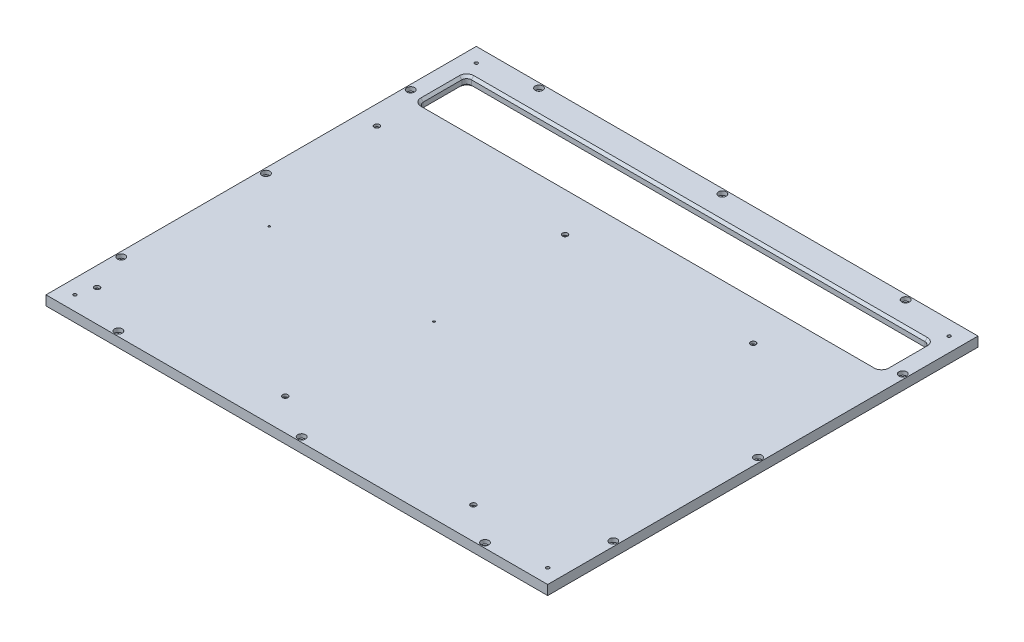
SolidWorks part; units mm, degrees
material "Bakelite Black"
ref_plane "Front" through (0, 0, 0) normal (0, 0, 1) x (1, 0, 0)
ref_plane "Top" through (0, 0, 0) normal (0, 1, 0) x (1, 0, 0)
ref_plane "Right" through (0, 0, 0) normal (1, 0, 0) x (0, 0, -1)
sketch "Sketch1" plane through (0, 0, 0) normal (0, 1, 0) x (1, 0, 0)
  line L1 (0, 0) -> (520, 0)
  line L2 (0, 0) -> (0, 446)
  line L3 (0, 446) -> (520, 446)
  line L4 (520, 0) -> (520, 446)
  dimension "D1" = 520
  dimension "D2" = 446
extrude "Boss-Extrude1" add sketch "Sketch1" along normal blind 10
sketch "Sketch4" plane through (0, 10, 0) normal (0, 1, 0) x (1, 0, 0)
  line L0 (520, 446) -> (0, 446) construction
  line L1 (500, 366) -> (20, 366)
  line L2 (500, 366) -> (500, 416)
  line L3 (500, 416) -> (20, 416)
  line L4 (20, 366) -> (20, 416)
  line L6 (260, 416) -> (260, 0) construction
  line L7 (20, 391) -> (500, 391) construction
  line L8 (0, 0) -> (520, 0) construction
  dimension "D1" = 240
  dimension "D2" = 30
  dimension "D3" = 50
extrude "Cut-Extrude1" cut sketch "Sketch4" against normal blind 10
fillet "Fillet1" radius 5 4 edges at (500, 5, -366) (20, 5, -416) (500, 5, -416) (20, 5, -366)
chamfer "Chamfer1" distance 2.5 angle 45 16 edges at (21.4645, 10, -367.4645) (260, 10, -366) (498.5355, 10, -367.4645) (500, 10, -391) (498.5355, 10, -414.5355) (260, 10, -416) (21.4645, 10, -414.5355) (20, 10, -391) (21.4645, 0, -367.4645) (20, 0, -391) (21.4645, 0, -414.5355) (260, 0, -416) (498.5355, 0, -414.5355) (500, 0, -391) (498.5355, 0, -367.4645) (260, 0, -366)
ref_plane "Plane1" through (260, 0, 0) normal (-1, 0, 0) x (0, 0, 1)
ref_plane "Plane2" through (0, 0, -223) normal (0, 0, 1) x (1, 0, 0)
hole_wizard "CBORE for M4 SHCS1" positions "Sketch5" profile "Sketch6" counterbore size "M4" standard "ANSI Metric"
sketch "Sketch5" plane through (0, 10, 0) normal (0, 1, 0) x (1, 0, 0)
  line L0 (260, 5.5) -> (260, -5.5) construction
  line L1 (-5.5, 223) -> (5.5, 223) construction
  line L3 (0, 0) -> (520, 0) construction
  line L4 (520, 446) -> (0, 446) construction
  line L5 (0, 446) -> (0, 0) construction
  line L6 (520, 0) -> (520, 446) construction
  point P0 (5, 373)
  point P2 (5, 223)
  point P4 (5, 73)
  point P6 (70, 5)
  point P8 (260, 5)
  point P10 (450, 5)
  point P12 (515, 73)
  point P14 (515, 223)
  point P16 (515, 373)
  point P18 (450, 441)
  point P20 (260, 441)
  point P22 (70, 441)
  dimension "D1" = 150
  dimension "D2" = 150
  dimension "D3" = 190
  dimension "D4" = 190
  dimension "D5" = 5
  dimension "D6" = 5
  dimension "D7" = 5
  dimension "D8" = 5
sketch "Sketch6" plane through (5, 10, -373) normal (1, 0, 0) x (0, 0, 1)
  line L0 (0, 0) -> (0, 13.3519)
  line L1 (0, 13.3519) -> (2.25, 12)
  line L2 (2.25, 12) -> (2.25, 4)
  line L3 (2.25, 4) -> (4, 4)
  line L4 (4, 4) -> (4, 0)
  line L5 (4, 0) -> (0, 0)
  line L10 (0, 13.3519) -> (-2.25, 12) construction
  line L11 (0, -6.35) -> (0, 107.95) construction
  dimension "Hole Dia." = 4.5
  dimension "Hole Depth" = 12
  dimension "C'Bore Dia." = 8
  dimension "C'Bore Depth" = 4
  dimension "Drill Angle" = 118
hole_wizard "M4x0.7 Tapped Hole1" positions "Sketch7" profile "Sketch8" tap size "M4x0.7" standard "ANSI Metric" end condition through all
sketch "Sketch7" plane through (0, 10, 0) normal (0, 1, 0) x (1, 0, 0)
  line L0 (520, 446) -> (0, 446) construction
  line L1 (0, 446) -> (0, 0) construction
  line L2 (520, 0) -> (520, 446) construction
  line L3 (0, 0) -> (520, 0) construction
  point P0 (15, 431)
  point P2 (505, 431)
  point P4 (15, 15)
  point P6 (505, 15)
  dimension "D1" = 15
  dimension "D2" = 15
  dimension "D3" = 15
  dimension "D4" = 15
sketch "Sketch8" plane through (15, 10, -431) normal (1, 0, 0) x (0, 0, 1)
  line L0 (0, 0) -> (0, 10)
  line L1 (0, 10) -> (1.65, 10)
  line L2 (1.65, 10) -> (1.65, 0)
  line L5 (1.65, 0) -> (0, 0)
  line L11 (0, -6.35) -> (0, 107.95) construction
  dimension "Thru Tap Drill Dia." = 3.3
  dimension "Thru Tap Drill Depth" = 10
cosmetic thread "Hole Thread1" parameters "D2"=4
cosmetic thread "Hole Thread2" parameters "D2"=4
cosmetic thread "Hole Thread3" parameters "D2"=4
cosmetic thread "Hole Thread4" parameters "D2"=4
hole_wizard "CBORE for M2.5 SHCS1" positions "Sketch9" profile "Sketch10" counterbore size "M2.5" standard "ANSI Metric" end condition through all
sketch "Sketch9" plane through (0, 10, 0) normal (0, 1, 0) x (1, 0, 0)
  line L0 (-5.5, 223) -> (5.5, 223) construction
  line L1 (260, 5.5) -> (260, -5.5) construction
  point P0 (20, 33)
  point P7 (215, 33)
  point P9 (410, 33)
  point P11 (410, 323)
  point P13 (215, 323)
  point P15 (20, 323)
  dimension "D1" = 190
  dimension "D2" = 240
  dimension "D3" = 290
  dimension "D4" = 195
  dimension "D5" = 195
sketch "Sketch10" plane through (20, 10, -33) normal (1, 0, 0) x (0, 0, 1)
  line L0 (0, 0) -> (0, 10)
  line L1 (0, 10) -> (1.45, 10)
  line L3 (1.45, 10) -> (1.45, 2.5)
  line L4 (1.45, 2.5) -> (2.75, 2.5)
  line L5 (2.75, 2.5) -> (2.75, 0)
  line L7 (2.75, 0) -> (0, 0)
  line L11 (0, -6.35) -> (0, 107.95) construction
  dimension "Thru Hole Dia." = 2.9
  dimension "Thru Hole Depth" = 10
  dimension "C'Bore Dia." = 5.5
  dimension "C'Bore Depth" = 2.5
hole_wizard "M2.5x0.45 Tapped Hole1" positions "Sketch11" profile "Sketch12" tap size "M2.5x0.45" standard "ANSI Metric" end condition through all
sketch "Sketch11" plane through (0, 10, 0) normal (0, 1, 0) x (1, 0, 0)
  line L0 (-5.5, 223) -> (5.5, 223) construction
  line L1 (260, 5.5) -> (260, -5.5) construction
  point P0 (54.288, 177.0876)
  point P2 (225.088, 177.0876)
  dimension "D1" = 170.8
  dimension "D2" = 45.9124
  dimension "D3" = 205.712
sketch "Sketch12" plane through (54.288, 10, -177.0876) normal (1, 0, 0) x (0, 0, 1)
  line L0 (0, 0) -> (0, 10)
  line L1 (0, 10) -> (1.025, 10)
  line L2 (1.025, 10) -> (1.025, 0)
  line L5 (1.025, 0) -> (0, 0)
  line L11 (0, -6.35) -> (0, 107.95) construction
  dimension "Thru Tap Drill Dia." = 2.05
  dimension "Thru Tap Drill Depth" = 10
cosmetic thread "Hole Thread5" parameters "D2"=2.5
cosmetic thread "Hole Thread6" parameters "D2"=2.5
